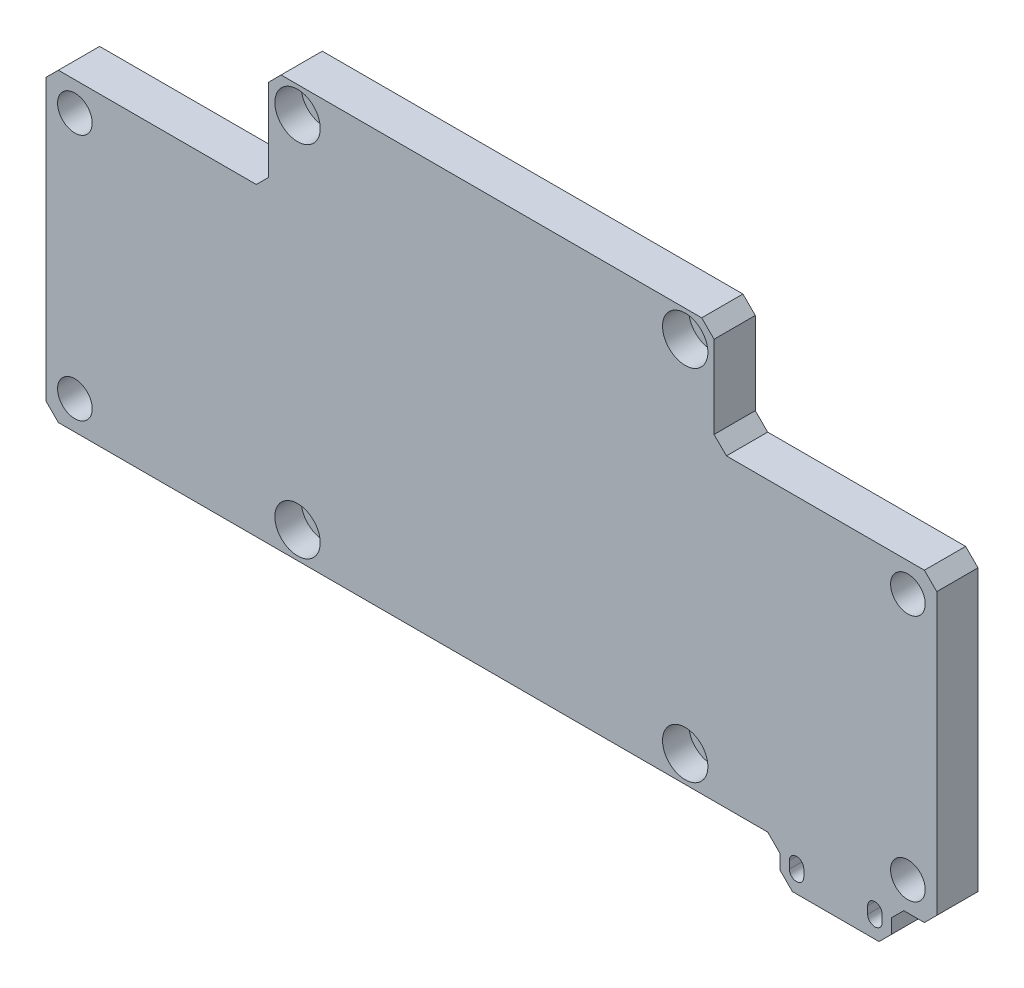
SolidWorks part; units mm, degrees
material "ABS"
ref_plane "Ebene vorne" through (0, 0, 0) normal (0, 0, 1) x (1, 0, 0)
ref_plane "Ebene oben" through (0, 0, 0) normal (0, 1, 0) x (1, 0, 0)
ref_plane "Ebene rechts" through (0, 0, 0) normal (1, 0, 0) x (0, 0, -1)
sketch "Skizze1" plane through (0, 0, 0) normal (0, 0, 1) x (1, 0, 0)
  line L1 (108, -50) -> (-108, -50)
  line L2 (108, -50) -> (108, 50)
  line L3 (108, 50) -> (-108, 50)
  line L4 (-108, -50) -> (-108, 50)
  line L5 (108, -50) -> (-108, 50) construction
  line L6 (108, 50) -> (-108, -50) construction
  point P0 (0, 0)
  dimension "D1" = 100
  dimension "D2" = 216
extrude "Aufsatz-Linear austragen1" add sketch "Skizze1" along normal blind 10
sketch "Skizze2" plane through (0, 0, 10) normal (0, 0, 1) x (1, 0, 0)
  line L1 (47, -43.5) -> (-47, -43.5)
  line L2 (47, -43.5) -> (47, 43.5)
  line L3 (47, 43.5) -> (-47, 43.5)
  line L4 (-47, -43.5) -> (-47, 43.5)
  line L5 (47, -43.5) -> (-47, 43.5) construction
  line L6 (47, 43.5) -> (-47, -43.5) construction
  point P0 (0, 0)
  dimension "D1" = 94
  dimension "D2" = 87
hole_wizard "Stirnsenkung für M6 Zylinderschraube mit Innensechskant1" positions "Skizze3" profile "Skizze4" counterbore size "M6" standard "DIN"
sketch "Skizze3" plane through (0, 0, 10) normal (0, 0, 1) x (1, 0, 0)
  point P0 (-47, -43.5)
  point P3 (47, -43.5)
sketch "Skizze4" plane through (-47, -43.5, 10) normal (1, 0, 0) x (0, -1, 0)
  line L0 (0, 0) -> (0, 16.9828)
  line L1 (0, 16.9828) -> (3.3, 15)
  line L2 (3.3, 15) -> (3.3, 6.4)
  line L3 (3.3, 6.4) -> (5.5, 6.4)
  line L4 (5.5, 6.4) -> (5.5, 0)
  line L5 (5.5, 0) -> (0, 0)
  line L10 (0, 16.9828) -> (-3.3, 15) construction
  line L11 (0, -6.35) -> (0, 107.95) construction
  dimension "Bohrerdurchmesser" = 6.6
  dimension "Bohrungstiefe" = 15
  dimension "Senkdurchmesser2" = 11
  dimension "Senktiefe2" = 6.4
  dimension "Spitzenwinkel" = 118
hole_wizard "CBORE for M6 Hex Socket Head Cap Screw1" positions "Skizze5" profile "Skizze6" counterbore size "M6" standard "DIN"
sketch "Skizze5" plane through (0, 0, 10) normal (0, 0, 1) x (1, 0, 0)
  point P0 (-47, 43.5)
  point P3 (47, 43.5)
sketch "Skizze6" plane through (-47, 43.5, 10) normal (1, 0, 0) x (0, -1, 0)
  line L0 (0, 0) -> (0, 16.9828)
  line L1 (0, 16.9828) -> (3.3, 15)
  line L2 (3.3, 15) -> (3.3, 6.4)
  line L3 (3.3, 6.4) -> (5.5, 6.4)
  line L4 (5.5, 6.4) -> (5.5, 0)
  line L5 (5.5, 0) -> (0, 0)
  line L10 (0, 16.9828) -> (-3.3, 15) construction
  line L11 (0, -6.35) -> (0, 107.95) construction
  dimension "Hole Dia." = 6.6
  dimension "Hole Depth" = 15
  dimension "C'Bore Dia." = 11
  dimension "C'Bore Depth" = 6.4
  dimension "Drill Angle" = 118
sketch "Skizze15" plane through (0, 0, 10) normal (0, 0, 1) x (1, 0, 0)
  line L0 (-108, -50) -> (108, -50) construction
  line L1 (101, -43) -> (-101, -43)
  line L2 (101, -43) -> (101, 17)
  line L3 (101, 17) -> (-101, 17)
  line L4 (-101, -43) -> (-101, 17)
  circle A0 centre (-47, 43.5) radius 3.3 construction
  dimension "D1" = 60
  dimension "D2" = 202
  dimension "D3" = 7
  dimension "D4" = 54
hole_wizard "M8 Clearance Hole1" positions "Skizze16" profile "Skizze17" hole size "M8" standard "ISO"
sketch "Skizze16" plane through (0, 0, 10) normal (0, 0, 1) x (1, 0, 0)
  point P0 (-101, 17)
  point P3 (-101, -43)
  point P6 (101, 17)
  point P9 (101, -43)
sketch "Skizze17" plane through (-101, 17, 10) normal (1, 0, 0) x (0, -1, 0)
  line L0 (0, 0) -> (0, 19.5236)
  line L1 (0, 19.5236) -> (4.2, 17)
  line L2 (4.2, 17) -> (4.2, 0)
  line L5 (4.2, 0) -> (0, 0)
  line L10 (0, 19.5236) -> (-4.2, 17) construction
  line L11 (0, -6.35) -> (0, 107.95) construction
  dimension "Bohrerdurchmesser" = 8.4
  dimension "Bohrungstiefe" = 17
  dimension "Spitzenwinkel" = 118
sketch "Skizze18" plane through (0, 0, 10) normal (0, 0, 1) x (1, 0, 0)
  line L0 (-108, -50) -> (108, -50) construction
  line L1 (-108, 50) -> (-54, 50)
  line L2 (-108, 50) -> (-108, 24)
  line L3 (-108, 24) -> (-54, 24)
  line L4 (-54, 50) -> (-54, 24)
  dimension "D1" = 74
  dimension "D2" = 54
extrude "Schnitt-Linear austragen1" cut sketch "Skizze18" against normal blind 15
mirror "Spiegeln1" about plane through (0, 0, 0) normal (1, 0, 0) of "Schnitt-Linear austragen1"
sketch "Sketch1" plane through (0, 24, 0) normal (0, 1, 0) x (1, 0, 0)
  line L0 (108, 0) -> (54, 0) construction
  line L1 (97, 0) -> (70, 0)
  line L2 (97, 0) -> (97, -10)
  line L3 (97, -10) -> (70, -10)
  line L4 (70, 0) -> (70, -10)
  line L5 (108, -10) -> (54, -10) construction
  line L7 (0, -55) -> (0, 55) construction
  dimension "D1" = 70
  dimension "D2" = 27
extrude "Boss-Extrude1" add sketch "Sketch1" along normal blind 9.5
sketch "Sketch3" plane through (0, 0, 0) normal (0, 0, -1) x (-1, 0, 0)
  line L0 (-93, 29.15) -> (-93, 27.35) construction
  line L1 (-91.25, 29.15) -> (-91.25, 27.35)
  line L2 (-94.75, 29.15) -> (-94.75, 27.35)
  line L4 (-97, 33.5) -> (-70, 33.5) construction
  line L5 (-97, 33.5) -> (-97, 24) construction
  arc A0 (-91.25, 29.15) -> (-94.75, 29.15) centre (-93, 29.15) ccw
  arc A1 (-94.75, 27.35) -> (-91.25, 27.35) centre (-93, 27.35) ccw
  point P2 (-93, 28.25)
  dimension "D1" = 3.5
  dimension "D2" = 1.8
  dimension "D3" = 5.25
  dimension "D4" = 4
extrude "Cut-Extrude1" cut sketch "Sketch3" against normal blind 10
pattern_linear "LPattern1" count 2 spacing 19 along (-1, 0, 0) of "Cut-Extrude1"
sketch "Sketch4" plane through (0, 0, 10) normal (0, 0, 1) x (1, 0, 0)
  line L1 (74, 32.3832) -> (71.2, 30.7666)
  line L2 (71.2, 30.7666) -> (71.2, 28.3753)
  line L5 (76.8, 28.3728) -> (76.8, 30.7666)
  line L6 (76.8, 30.7666) -> (74, 32.3832)
  line L7 (71.2, 27.5334) -> (74, 25.9168) [skipped]
  line L8 (74, 25.9168) -> (76.8, 27.5334) [skipped]
  line L16 (74, 24.1168) -> (76.8, 25.7334)
  line L18 (76.8, 25.7334) -> (76.8, 28.3728)
  line L21 (71.2, 28.3753) -> (71.2, 25.7334)
  line L22 (71.2, 25.7334) -> (74, 24.1168)
  line L23 (74, 30.5832) -> (71.2, 28.9666) [skipped]
  line L24 (76.8, 28.9666) -> (74, 30.5832) [skipped]
  circle A0 centre (74, 29.15) radius 2.8 construction
  circle A1 centre (74, 27.35) radius 2.8 construction
  dimension "D2" = 5.6
  dimension "D1" = 5.6
extrude "Cut-Extrude2" cut sketch "Sketch4" along normal blind 3 from offset 10 offset against normal yes
pattern_linear "LPattern2" count 2 spacing 19 along (1, 0, 0) of "Cut-Extrude2"
ref_plane "Plane1" through (0, -13, 0) normal (0, 1, 0) x (1, 0, 0)
mirror "Mirror1" about plane through (0, -13, 0) normal (0, 1, 0) of "LPattern2", "Cut-Extrude2", "LPattern1", "Cut-Extrude1", "Boss-Extrude1"
sketch "Sketch5" plane through (0, 0, 10) normal (0, 0, 1) x (1, 0, 0)
  line L1 (70, 33.5) -> (97, 33.5)
  line L2 (70, 33.5) -> (70, 24)
  line L3 (70, 24) -> (97, 24)
  line L4 (97, 33.5) -> (97, 24)
extrude "Cut-Extrude3" cut sketch "Sketch5" against normal blind 10
sketch "Sketch6" plane through (0, 0, 10) normal (0, 0, 1) x (1, 0, 0)
  line L1 (54, 24) -> (84, 24)
  line L2 (54, 24) -> (54, 59)
  line L3 (54, 59) -> (84, 59)
  line L4 (84, 24) -> (84, 59)
  circle A0 centre (69, 55) radius 1.75
  circle A1 centre (69, 47) radius 1.75
  dimension "D3" = 3.5
  dimension "D4" = 3.5
  dimension "D7" = 4
  dimension "D8" = 8
  dimension "D1" = 30
  dimension "D2" = 35
  dimension "D5" = 15
  dimension "D6" = 15
ref_plane "Plane2" through (0, 0, 20) normal (0, 0, 1) x (1, 0, 0)
chamfer "Chamfer4" distance 3 angle 45 6 edges at (-54, 24, 5) (54, 24, 5) (70, -59.5, 5) (97, -59.5, 5) (97, -50, 5) (70, -50, 5)
sketch "Sketch8" plane through (0, 0, 10) normal (0, 0, 1) x (1, 0, 0)
  line L0 (-54, 38.5) -> (54, 38.5) construction
  line L1 (-54, 27) -> (-54, 50) construction
  line L2 (54, 27) -> (54, 50) construction
  text T0 "<b>CAROLOGISTICS</b>" font "Century Gothic" height 8
chamfer "Chamfer5" distance 3 angle 45 6 edges at (-54, 50, 5) (54, 50, 5) (108, -50, 5) (108, 24, 5) (-108, -50, 5) (-108, 24, 5)
